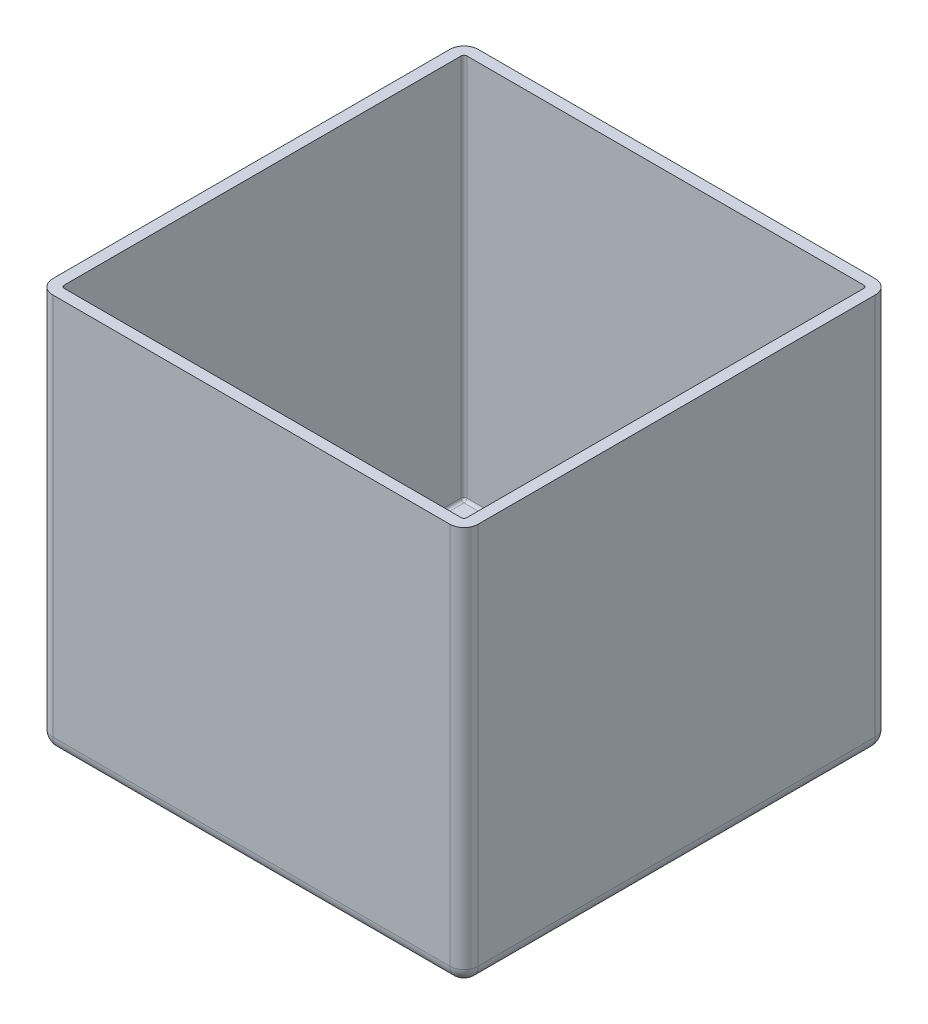
SolidWorks part; units mm, degrees
ref_plane "Front Plane" through (0, 0, 0) normal (0, 0, 1) x (1, 0, 0)
ref_plane "Top Plane" through (0, 0, 0) normal (0, 1, 0) x (1, 0, 0)
ref_plane "Right Plane" through (0, 0, 0) normal (1, 0, 0) x (0, 0, -1)
sketch "Sketch1" plane through (0, 0, 0) normal (0, 1, 0) x (1, 0, 0)
  line L1 (-30, -30) -> (30, -30)
  line L2 (-30, -30) -> (-30, 30)
  line L3 (-30, 30) -> (30, 30)
  line L4 (30, -30) -> (30, 30)
  line L5 (-30, -30) -> (30, 30) construction
  line L6 (-30, 30) -> (30, -30) construction
  point P0 (0, 0)
  dimension "D1" = 60
  dimension "D2" = 60
extrude "Boss-Extrude1" add sketch "Sketch1" along normal blind 56
fillet "Fillet1" radius 2 8 edges at (-30, 0, 0) (0, 0, -30) (30, 0, 0) (0, 0, 30) (-30, 28, -30) (-30, 28, 30) (30, 28, -30) (30, 28, 30)
shell "Shell1" thickness 1.6 removed face at (0, 56, 0)
sketch "Sketch2" plane through (0, 1.6, 0) normal (0, 1, 0) x (1, 0, 0)
  line L28 (18.8649, 1.6027) -> (12.7611, 8.2248)
  line L29 (8.3493, 10.1583) -> (-8.2959, 10.1583)
  line L30 (-12.7077, 8.2248) -> (-18.8115, 1.6027)
  line L31 (-12.7077, -8.4082) -> (-18.8115, -1.7861)
  line L32 (8.3493, -10.3417) -> (-8.2959, -10.3417)
  line L33 (18.8649, -1.7861) -> (12.7611, -8.4082)
  line L34 (20.3355, 2.9582) -> (14.2317, 9.5803)
  line L35 (8.3493, 12.1583) -> (-8.2959, 12.1583)
  line L36 (-14.1783, 9.5803) -> (-20.2821, 2.9582)
  line L37 (-14.1783, -9.7637) -> (-20.2821, -3.1416)
  line L38 (8.3493, -12.3417) -> (-8.2959, -12.3417)
  line L39 (20.3355, -3.1416) -> (14.2317, -9.7637)
  arc A20 (12.7611, 8.2248) -> (8.3493, 10.1583) centre (8.3493, 4.1583) ccw
  arc A21 (-8.2959, 10.1583) -> (-12.7077, 8.2248) centre (-8.2959, 4.1583) ccw
  arc A22 (-18.8115, 1.6027) -> (-18.8115, -1.7861) centre (-16.9733, -0.0917) ccw
  arc A23 (-8.2959, -10.3417) -> (-12.7077, -8.4082) centre (-8.2959, -4.3417) cw
  arc A24 (12.7611, -8.4082) -> (8.3493, -10.3417) centre (8.3493, -4.3417) cw
  arc A25 (18.8649, 1.6027) -> (18.8649, -1.7861) centre (17.0267, -0.0917) cw
  arc A26 (14.2317, 9.5803) -> (8.3493, 12.1583) centre (8.3493, 4.1583) ccw
  arc A27 (-8.2959, 12.1583) -> (-14.1783, 9.5803) centre (-8.2959, 4.1583) ccw
  arc A28 (-20.2821, 2.9582) -> (-20.2821, -3.1416) centre (-16.9733, -0.0917) ccw
  arc A29 (-8.2959, -12.3417) -> (-14.1783, -9.7637) centre (-8.2959, -4.3417) cw
  arc A30 (14.2317, -9.7637) -> (8.3493, -12.3417) centre (8.3493, -4.3417) cw
  arc A31 (20.3355, 2.9582) -> (20.3355, -3.1416) centre (17.0267, -0.0917) cw
  dimension "D1" = 2
extrude "Cut-Extrude1" cut sketch "Sketch2" against normal through all contours L28 A20 L29 A21 L30 A22 L31 A23 L32 A24 L33 A25
extrude "Boss-Extrude2" add sketch "Sketch2<4>" along normal blind 8
sketch "Sketch2<4>" plane through (0, 1.6, 0) normal (0, 1, 0) x (1, 0, 0) same geometry as "Sketch2"
sketch "Sketch3" plane through (0, 0, -12.1583) normal (0, 0, -1) x (-1, 0, 0)
  line L0 (-0.0267, 9.6) -> (-0.0267, 1.6) construction
  line L1 (-8.3493, 9.6) -> (8.2959, 9.6) construction
  circle A0 centre (-0.0267, 5.6) radius 2.4
extrude "Cut-Extrude2" cut sketch "Sketch3" against normal up to surface (24.5 mm away) up to face at (0.0267, 5.6, 12.3417)
